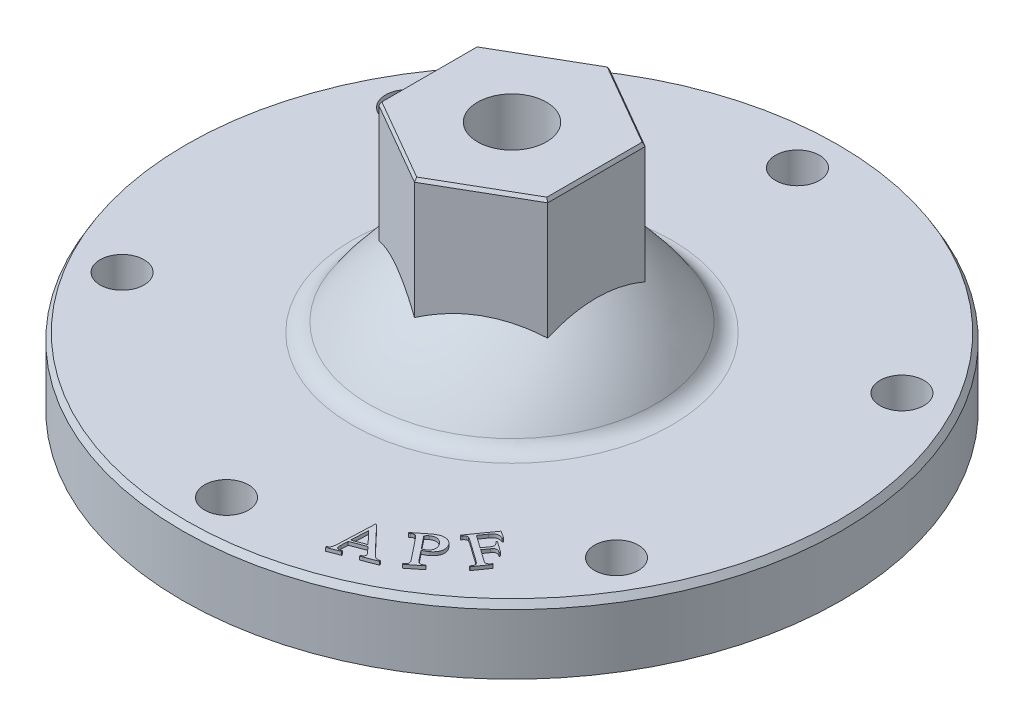
SolidWorks part; units mm, degrees
material "Brass"
ref_plane "Front Plane" through (0, 0, 0) normal (0, 0, 1) x (1, 0, 0)
ref_plane "Top Plane" through (0, 0, 0) normal (0, 1, 0) x (1, 0, 0)
ref_plane "Right Plane" through (0, 0, 0) normal (1, 0, 0) x (0, 0, -1)
sketch "Sketch1" plane through (0, 0, 0) normal (0, 1, 0) x (1, 0, 0)
  circle A0 centre (0, 0) radius 48.8
  dimension "D1" = 97.6
extrude "Boss-Extrude1" add sketch "Sketch1" along normal blind 10.5
sketch "Sketch2" plane through (0, 0, 0) normal (0, 0, 1) x (1, 0, 0)
  line L0 (0, 0) -> (0, 27.0216) construction
  line L1 (48.8, 10.5) -> (-48.8, 10.5) construction
  line L2 (-12.25, 21.4) -> (0, 21.4)
  line L3 (-22, 10.5) -> (0, 10.5)
  line L4 (0, 21.4) -> (0, 10.5)
  arc A0 (-12.25, 21.4) -> (-22, 10.5) centre (9.2028, -7.6001) ccw
  dimension "D1" = 10.9
  dimension "D2" = 22
  dimension "D3" = 12.25
revolve "Revolve2" add sketch "Sketch2" angle 360 about L0
sketch "Sketch4" plane through (0, 10.5, 0) normal (0, 1, 0) x (1, 0, 0)
  line L1 (0, 14.4338) -> (-12.5, 7.2169)
  line L2 (-12.5, 7.2169) -> (-12.5, -7.2169)
  line L3 (-12.5, -7.2169) -> (0, -14.4338)
  line L4 (0, -14.4338) -> (12.5, -7.2169)
  line L5 (12.5, -7.2169) -> (12.5, 7.2169)
  line L6 (12.5, 7.2169) -> (0, 14.4338)
  circle A0 centre (0, 0) radius 12.5 construction
  dimension "D1" = 25
extrude "Boss-Extrude2" add sketch "Sketch4" along normal blind 27
fillet "Fillet1" radius 3 1 edges at (0, 10.5, -22)
hole_wizard "M12x1.75 Tapped Hole1" positions "Sketch7" profile "Sketch6" tap size "M12x1.75" standard "ANSI Metric" end condition up to next
sketch "Sketch7" plane through (0, 37.5, 0) normal (0, 1, 0) x (1, 0, 0)
  point P0 (0, 0)
sketch "Sketch6" plane through (0, 37.5, 0) normal (1, 0, 0) x (0, 0, 1)
  line L0 (0, 0) -> (0, 37.5)
  line L1 (0, 37.5) -> (5.1, 37.5)
  line L2 (5.1, 37.5) -> (5.1, 0)
  line L5 (5.1, 0) -> (0, 0)
  line L11 (0, -6.35) -> (0, 107.95) construction
  dimension "Thru Tap Drill Dia." = 10.2
  dimension "Thru Tap Drill Depth" = 37.5
cosmetic thread "Hole Thread1" parameters "D2"=12
sketch "Sketch8" plane through (0, 10.5, 0) normal (0, 1, 0) x (1, 0, 0)
  circle A0 centre (0, 42.25) radius 3.25
  circle A1 centre (0, 0) radius 48.8 construction
  dimension "D1" = 6.5
  dimension "D2" = 42.25
extrude "Cut-Extrude1" cut sketch "Sketch8" against normal up to next
pattern_circular "CirPattern1" count 6 over 360 about axis through (0, 0, 0) along (0, 1, 0) of "Cut-Extrude1"
sketch "Sketch9" plane through (0, 10.5, 0) normal (0, 1, 0) x (1, 0, 0)
  arc A0 (3.25, -42.25) -> (33.3396, -21.125) centre (7.7323, -16.6427) ccw construction
  circle A1 centre (0, -42.25) radius 3.25 construction
  circle A2 centre (36.5896, -21.125) radius 3.25 construction
  text T0 "     A P F" font "Times New Roman" height in points 24
extrude "Boss-Extrude3" add sketch "Sketch9" along normal blind 0.5
sketch "Sketch10" plane through (0, 0, 0) normal (0, -1, 0) x (1, 0, 0)
  circle A0 centre (0, 0) radius 34.9
  dimension "D1" = 69.8
extrude "Boss-Extrude4" add sketch "Sketch10" along normal blind 2.5
sketch "Sketch11" plane through (0, -2.5, 0) normal (0, -1, 0) x (1, 0, 0)
  circle A0 centre (0, 0) radius 32.7
  circle A1 centre (0, 0) radius 31.45
  dimension "D1" = 65.4
  dimension "D2" = 62.9
extrude "Cut-Extrude2" cut sketch "Sketch11" against normal blind 0.5
chamfer "Chamfer1" distance 0.78 angle 30 2 edges at (0, -2, -31.45) (0, -2, -32.7)
sketch "Sketch12" plane through (0, -2.5, 0) normal (0, -1, 0) x (1, 0, 0)
  circle A0 centre (0, 0) radius 29.95
  circle A1 centre (0, 0) radius 28.9
  dimension "D1" = 59.9
  dimension "D2" = 57.8
extrude "Cut-Extrude3" cut sketch "Sketch12" against normal blind 0.5
chamfer "Chamfer2" distance 0.65 angle 30 2 edges at (0, -2, -28.9) (0, -2, -29.95)
sketch "Sketch13" plane through (0, -2.5, 0) normal (0, -1, 0) x (1, 0, 0)
  circle A0 centre (0, 0) radius 27.45
  circle A1 centre (0, 0) radius 26.4
  dimension "D1" = 54.9
  dimension "D2" = 52.8
extrude "Cut-Extrude4" cut sketch "Sketch13" against normal blind 0.5
chamfer "Chamfer3" distance 0.66 angle 30 2 edges at (0, -2, -27.45) (0, -2, -26.4)
sketch "Sketch14" plane through (0, -2.5, 0) normal (0, -1, 0) x (1, 0, 0)
  circle A0 centre (0, 0) radius 24.4
  circle A1 centre (0, 0) radius 23.4
  dimension "D1" = 48.8
  dimension "D2" = 46.8
extrude "Cut-Extrude5" cut sketch "Sketch14" against normal blind 0.5
chamfer "Chamfer4" distance 0.63 angle 30 2 edges at (0, -2, -24.4) (0, -2, -23.4)
sketch "Sketch15" plane through (0, -2.5, 0) normal (0, -1, 0) x (1, 0, 0)
  circle A0 centre (0, 0) radius 19.9
  dimension "D1" = 39.8
extrude "Cut-Extrude6" cut sketch "Sketch15" against normal blind 6.5
ref_plane "Plane1" through (0, 7.3, 0) normal (0, -1, 0) x (-1, 0, 0)
sketch "Sketch16" plane through (0, 7.3, 0) normal (0, -1, 0) x (-1, 0, 0)
  circle A0 centre (0, 0) radius 14
  dimension "D1" = 28
sketch "Sketch17" plane through (0, 4, 0) normal (0, -1, 0) x (1, 0, 0)
  circle A0 centre (0, 0) radius 19.9
  dimension "D1" = 39.8
loft "Cut-Loft1" cut profiles "Sketch17", "Sketch16"
sketch "Sketch18" plane through (0, 7.3, 0) normal (0, -1, 0) x (1, 0, 0)
  circle A0 centre (0, 0) radius 14
  dimension "D1" = 28
extrude "Cut-Extrude7" cut sketch "Sketch18" against normal blind 2.9
fillet "Fillet2" radius 2 1 edges at (0, -2.5, -19.9)
ref_plane "Plane2" through (0, 16, 0) normal (0, -1, 0) x (-1, 0, 0)
sketch "Sketch19" plane through (0, 16, 0) normal (0, -1, 0) x (-1, 0, 0)
  circle A0 centre (0, 0) radius 8.05
  dimension "D1" = 16.1
sketch "Sketch20" plane through (0, 10.2, 0) normal (0, -1, 0) x (1, 0, 0)
  circle A0 centre (0, 0) radius 14
  dimension "D1" = 28
loft "Cut-Loft2" cut profiles "Sketch20", "Sketch19"
sketch "Sketch21" plane through (0, 16, 0) normal (0, -1, 0) x (1, 0, 0)
  circle A0 centre (0, 0) radius 8.05
  dimension "D1" = 16.1
extrude "Cut-Extrude8" cut sketch "Sketch21" against normal blind 5.4
chamfer "Chamfer5" distance 1 angle 30 2 edges at (0, 0, 48.8) (0, 10.5, 48.8)
chamfer "Chamfer6" distance 0.5 angle 30 6 edges at (-6.25, 37.5, -10.8253) (-12.5, 37.5, 0) (-6.25, 37.5, 10.8253) (6.25, 37.5, 10.8253) (6.25, 37.5, -10.8253) (12.5, 37.5, 0)
fillet "Fillet3" radius 0.3 2 edges
